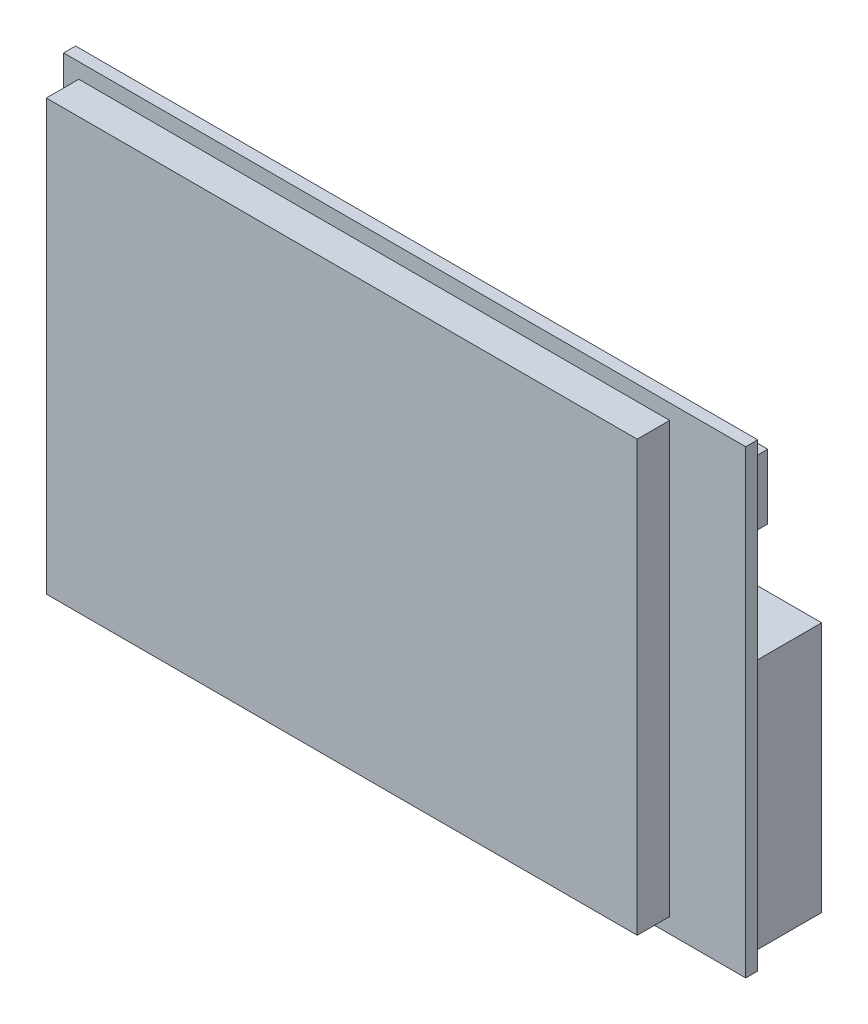
SolidWorks part; units mm, degrees
ref_plane "Front Plane" through (0, 0, 0) normal (0, 0, 1) x (1, 0, 0)
ref_plane "Top Plane" through (0, 0, 0) normal (0, 1, 0) x (1, 0, 0)
ref_plane "Right Plane" through (0, 0, 0) normal (1, 0, 0) x (0, 0, -1)
sketch "Sketch1" plane through (0, 0, 0) normal (0, 0, -1) x (-1, 0, 0)
  line L1 (-32.25, -24.25) -> (32.25, -24.25) construction
  line L2 (-32.25, -24.25) -> (-32.25, 24.25) construction
  line L3 (-32.25, 24.25) -> (32.25, 24.25) construction
  line L4 (32.25, -24.25) -> (32.25, 24.25) construction
  line L5 (-32.25, -24.25) -> (32.25, 24.25) construction
  line L6 (-32.25, 24.25) -> (32.25, -24.25) construction
  line L7 (-36, 28) -> (41.7, 28) construction
  line L8 (-36, 28) -> (-36, -28.5) construction
  line L9 (-36, -28.5) -> (41.7, -28.5) construction
  line L10 (41.7, 28) -> (41.7, -28.5) construction
  line L11 (-46, 30) -> (43.7, 30)
  line L12 (-46, 30) -> (-46, -30.5)
  line L13 (-46, -30.5) -> (43.7, -30.5)
  line L14 (43.7, 30) -> (43.7, -30.5)
  point P0 (0, 0)
  dimension "D1" = 64.5
  dimension "D2" = 48.5
  dimension "D3" = 3.75
  dimension "D4" = 3.75
  dimension "D5" = 56.5
  dimension "D6" = 77.7
  dimension "D7" = 2
  dimension "D8" = 10
  dimension "D9" = 2
  dimension "D10" = 2
extrude "Boss-Extrude1" add sketch "Sketch1" along normal blind 1.5748
sketch "Sketch2" plane through (0, 0, 0) normal (0, 0, -1) x (-1, 0, 0)
  line L1 (-36, -28.5) -> (41.7, -28.5)
  line L2 (-36, -28.5) -> (-36, 28)
  line L3 (-36, 28) -> (41.7, 28)
  line L4 (41.7, -28.5) -> (41.7, 28)
  line L5 (41.7, 28) -> (49.6841, 28) construction
  line L6 (-36, 28) -> (-43.9841, 28) construction
  line L10 (-32.25, -24.25) -> (32.25, -24.25) construction
  line L11 (-32.25, -24.25) -> (-32.25, 24.25) construction
  line L12 (-32.25, 24.25) -> (32.25, 24.25) construction
  line L13 (32.25, -24.25) -> (32.25, 24.25) construction
  line L14 (-32.25, -24.25) -> (32.25, 24.25) construction
  line L15 (-32.25, 24.25) -> (32.25, -24.25) construction
  point P0 (0, 0)
  point P14 (0, 0)
  dimension "D1" = 56.5
  dimension "D2" = 77.7
  dimension "D3" = 3.75
  dimension "D4" = 48.5
  dimension "D5" = 64.5
  dimension "D6" = 3.75
extrude "Boss-Extrude2" add sketch "Sketch2" against normal blind 4.27
sketch "Sketch3" plane through (0, 0, -1.5748) normal (0, 0, 1) x (1, 0, 0)
  line L1 (45.5416, 4.5) -> (36.5816, 4.5)
  line L2 (45.5416, 4.5) -> (45.5416, -28.5)
  line L3 (45.5416, -28.5) -> (36.5816, -28.5)
  line L4 (36.5816, 4.5) -> (36.5816, -28.5)
  dimension "D1" = 33
  dimension "D2" = 8.96
extrude "Boss-Extrude3" add sketch "Sketch3" against normal blind 8.87
sketch "Sketch4" plane through (0, 0, -1.5748) normal (0, 0, 1) x (1, 0, 0)
  line L1 (38.0878, 25.594) -> (43.3178, 25.594)
  line L2 (38.0878, 25.594) -> (38.0878, 17.064)
  line L3 (38.0878, 17.064) -> (43.3178, 17.064)
  line L4 (43.3178, 25.594) -> (43.3178, 17.064)
  dimension "D1" = 8.53
  dimension "D2" = 5.23
extrude "Boss-Extrude4" add sketch "Sketch4" against normal blind 4
